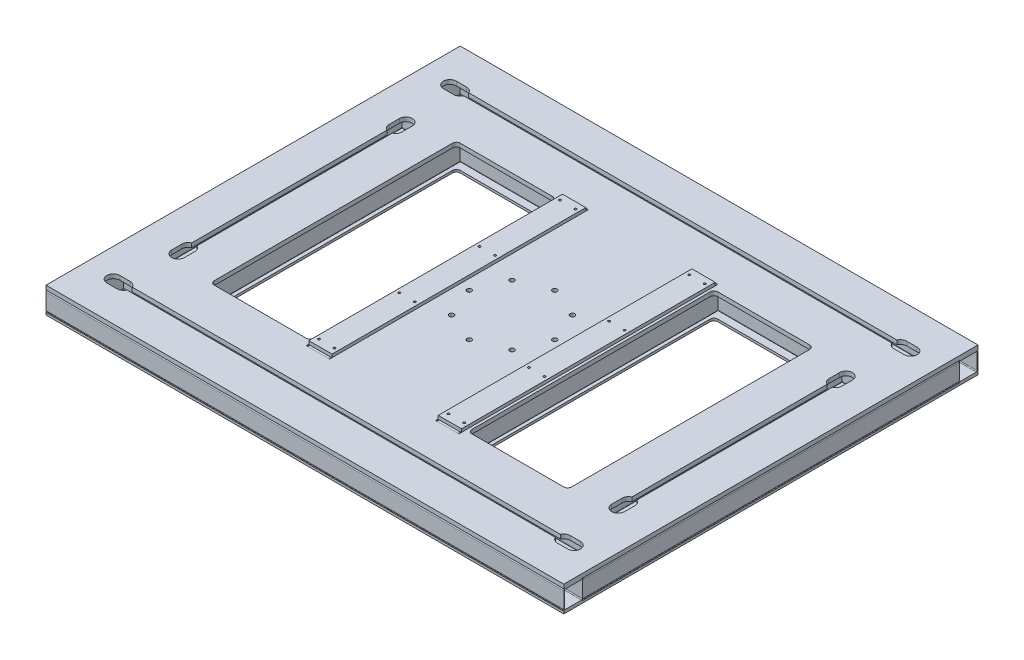
SolidWorks part; units mm, degrees
ref_plane "正面" through (0, 0, 0) normal (0, 0, 1) x (1, 0, 0)
ref_plane "平面" through (0, 0, 0) normal (0, 1, 0) x (1, 0, 0)
ref_plane "右側面" through (0, 0, 0) normal (1, 0, 0) x (0, 0, -1)
sketch "ｽｹｯﾁ1" plane through (0, 0, 0) normal (0, 1, 0) x (1, 0, 0)
  line L0 (-1000, -800) -> (1000, -800)
  line L1 (1000, -800) -> (1000, 800)
  line L2 (1000, 800) -> (-1000, 800)
  line L3 (-1000, 800) -> (-1000, -800)
extrude "ﾎﾞｽ - 押し出し1" add sketch "ｽｹｯﾁ1" along normal blind 9
sketch "ｽｹｯﾁ2" plane through (0, 0, 0) normal (0, 1, 0) x (1, 0, 0)
  line L0 (-675, -475) -> (-320, -475)
  line L1 (-305, -460) -> (-305, 460)
  line L2 (-320, 475) -> (-675, 475)
  line L3 (-690, 460) -> (-690, -460)
  line L4 (320, -475) -> (675, -475)
  line L5 (690, -460) -> (690, 460)
  line L6 (675, 475) -> (320, 475)
  line L7 (305, 460) -> (305, -460)
  arc A0 (-320, -475) -> (-305, -460) centre (-320, -460) ccw
  arc A1 (-305, 460) -> (-320, 475) centre (-320, 460) ccw
  arc A2 (-675, 475) -> (-690, 460) centre (-675, 460) ccw
  arc A3 (-690, -460) -> (-675, -475) centre (-675, -460) ccw
  arc A4 (675, -475) -> (690, -460) centre (675, -460) ccw
  arc A5 (690, 460) -> (675, 475) centre (675, 460) ccw
  arc A6 (320, 475) -> (305, 460) centre (320, 460) ccw
  arc A7 (305, -460) -> (320, -475) centre (320, -460) ccw
extrude "ｶｯﾄ - 押し出し1" cut sketch "ｽｹｯﾁ2" against normal through all and the other way through all
sketch "ｽｹｯﾁ3" plane through (0, 0, 0) normal (0, 1, 0) x (1, 0, 0)
  line L0 (-885, -475) -> (-815, -475)
  line L1 (-800, -460) -> (-800, 460)
  line L2 (-815, 475) -> (-885, 475)
  line L3 (-900, 460) -> (-900, -460)
  line L4 (815, -475) -> (885, -475)
  line L5 (900, -460) -> (900, 460)
  line L6 (885, 475) -> (815, 475)
  line L7 (800, 460) -> (800, -460)
  arc A0 (-815, -475) -> (-800, -460) centre (-815, -460) ccw
  arc A1 (-800, 460) -> (-815, 475) centre (-815, 460) ccw
  arc A2 (-885, 475) -> (-900, 460) centre (-885, 460) ccw
  arc A3 (-900, -460) -> (-885, -475) centre (-885, -460) ccw
  arc A4 (885, -475) -> (900, -460) centre (885, -460) ccw
  arc A5 (900, 460) -> (885, 475) centre (885, 460) ccw
  arc A6 (815, 475) -> (800, 460) centre (815, 460) ccw
  arc A7 (800, -460) -> (815, -475) centre (815, -460) ccw
extrude "ｶｯﾄ - 押し出し2" cut sketch "ｽｹｯﾁ3" against normal through all and the other way through all
sketch "ｽｹｯﾁ4" plane through (0, 0, 0) normal (0, 1, 0) x (1, 0, 0)
  line L0 (-885, -700) -> (885, -700)
  line L1 (900, -685) -> (900, -615)
  line L2 (885, -600) -> (-885, -600)
  line L3 (-900, -615) -> (-900, -685)
  line L4 (-885, 600) -> (885, 600)
  line L5 (900, 615) -> (900, 685)
  line L6 (885, 700) -> (-885, 700)
  line L7 (-900, 685) -> (-900, 615)
  arc A0 (885, -700) -> (900, -685) centre (885, -685) ccw
  arc A1 (900, -615) -> (885, -600) centre (885, -615) ccw
  arc A2 (-885, -600) -> (-900, -615) centre (-885, -615) ccw
  arc A3 (-900, -685) -> (-885, -700) centre (-885, -685) ccw
  arc A4 (885, 600) -> (900, 615) centre (885, 615) ccw
  arc A5 (900, 685) -> (885, 700) centre (885, 685) ccw
  arc A6 (-885, 700) -> (-900, 685) centre (-885, 685) ccw
  arc A7 (-900, 615) -> (-885, 600) centre (-885, 615) ccw
extrude "ｶｯﾄ - 押し出し3" cut sketch "ｽｹｯﾁ4" against normal through all and the other way through all
sketch "ｽｹｯﾁ5" plane through (0, 0, 0) normal (1, 0, 0) x (0, 0, -1)
  line L0 (-793.6, 9) -> (-731.4, 9)
  line L1 (-725, 15.4) -> (-725, 77.6)
  line L2 (-731.4, 84) -> (-793.6, 84)
  line L3 (-800, 77.6) -> (-800, 15.4)
  line L4 (-793.6, 12.2) -> (-731.4, 12.2)
  line L5 (-728.2, 15.4) -> (-728.2, 77.6)
  line L6 (-731.4, 80.8) -> (-793.6, 80.8)
  line L7 (-796.8, 77.6) -> (-796.8, 15.4)
  line L8 (731.4, 9) -> (793.6, 9)
  line L9 (800, 15.4) -> (800, 77.6)
  line L10 (793.6, 84) -> (731.4, 84)
  line L11 (725, 77.6) -> (725, 15.4)
  line L12 (731.4, 12.2) -> (793.6, 12.2)
  line L13 (796.8, 15.4) -> (796.8, 77.6)
  line L14 (793.6, 80.8) -> (731.4, 80.8)
  line L15 (728.2, 77.6) -> (728.2, 15.4)
  arc A0 (-731.4, 9) -> (-725, 15.4) centre (-731.4, 15.4) ccw
  arc A1 (-725, 77.6) -> (-731.4, 84) centre (-731.4, 77.6) ccw
  arc A2 (-793.6, 84) -> (-800, 77.6) centre (-793.6, 77.6) ccw
  arc A3 (-800, 15.4) -> (-793.6, 9) centre (-793.6, 15.4) ccw
  arc A4 (-731.4, 12.2) -> (-728.2, 15.4) centre (-731.4, 15.4) ccw
  arc A5 (-728.2, 77.6) -> (-731.4, 80.8) centre (-731.4, 77.6) ccw
  arc A6 (-793.6, 80.8) -> (-796.8, 77.6) centre (-793.6, 77.6) ccw
  arc A7 (-796.8, 15.4) -> (-793.6, 12.2) centre (-793.6, 15.4) ccw
  arc A8 (793.6, 9) -> (800, 15.4) centre (793.6, 15.4) ccw
  arc A9 (800, 77.6) -> (793.6, 84) centre (793.6, 77.6) ccw
  arc A10 (731.4, 84) -> (725, 77.6) centre (731.4, 77.6) ccw
  arc A11 (725, 15.4) -> (731.4, 9) centre (731.4, 15.4) ccw
  arc A12 (793.6, 12.2) -> (796.8, 15.4) centre (793.6, 15.4) ccw
  arc A13 (796.8, 77.6) -> (793.6, 80.8) centre (793.6, 77.6) ccw
  arc A14 (731.4, 80.8) -> (728.2, 77.6) centre (731.4, 77.6) ccw
  arc A15 (728.2, 15.4) -> (731.4, 12.2) centre (731.4, 15.4) ccw
extrude "ﾎﾞｽ - 押し出し2" add sketch "ｽｹｯﾁ5" against normal blind 1000 and the other way blind 1000
sketch "ｽｹｯﾁ6" plane through (0, 0, 0) normal (1, 0, 0) x (0, 0, -1)
  line L0 (-568.6, 9) -> (-506.4, 9)
  line L1 (-500, 15.4) -> (-500, 77.6)
  line L2 (-506.4, 84) -> (-568.6, 84)
  line L3 (-575, 77.6) -> (-575, 15.4)
  line L4 (-568.6, 12.2) -> (-506.4, 12.2)
  line L5 (-503.2, 15.4) -> (-503.2, 77.6)
  line L6 (-506.4, 80.8) -> (-568.6, 80.8)
  line L7 (-571.8, 77.6) -> (-571.8, 15.4)
  line L8 (506.4, 9) -> (568.6, 9)
  line L9 (575, 15.4) -> (575, 77.6)
  line L10 (568.6, 84) -> (506.4, 84)
  line L11 (500, 77.6) -> (500, 15.4)
  line L12 (506.4, 12.2) -> (568.6, 12.2)
  line L13 (571.8, 15.4) -> (571.8, 77.6)
  line L14 (568.6, 80.8) -> (506.4, 80.8)
  line L15 (503.2, 77.6) -> (503.2, 15.4)
  arc A0 (-506.4, 9) -> (-500, 15.4) centre (-506.4, 15.4) ccw
  arc A1 (-500, 77.6) -> (-506.4, 84) centre (-506.4, 77.6) ccw
  arc A2 (-568.6, 84) -> (-575, 77.6) centre (-568.6, 77.6) ccw
  arc A3 (-575, 15.4) -> (-568.6, 9) centre (-568.6, 15.4) ccw
  arc A4 (-506.4, 12.2) -> (-503.2, 15.4) centre (-506.4, 15.4) ccw
  arc A5 (-503.2, 77.6) -> (-506.4, 80.8) centre (-506.4, 77.6) ccw
  arc A6 (-568.6, 80.8) -> (-571.8, 77.6) centre (-568.6, 77.6) ccw
  arc A7 (-571.8, 15.4) -> (-568.6, 12.2) centre (-568.6, 15.4) ccw
  arc A8 (568.6, 9) -> (575, 15.4) centre (568.6, 15.4) ccw
  arc A9 (575, 77.6) -> (568.6, 84) centre (568.6, 77.6) ccw
  arc A10 (506.4, 84) -> (500, 77.6) centre (506.4, 77.6) ccw
  arc A11 (500, 15.4) -> (506.4, 9) centre (506.4, 15.4) ccw
  arc A12 (568.6, 12.2) -> (571.8, 15.4) centre (568.6, 15.4) ccw
  arc A13 (571.8, 77.6) -> (568.6, 80.8) centre (568.6, 77.6) ccw
  arc A14 (506.4, 80.8) -> (503.2, 77.6) centre (506.4, 77.6) ccw
  arc A15 (503.2, 15.4) -> (506.4, 12.2) centre (506.4, 15.4) ccw
extrude "ﾎﾞｽ - 押し出し3" add sketch "ｽｹｯﾁ6" against normal blind 925 and the other way blind 925
sketch "ｽｹｯﾁ7" plane through (0, 0, 0) normal (0, 0, 1) x (1, 0, 0)
  line L0 (-993.6, 9) -> (-931.4, 9)
  line L1 (-925, 15.4) -> (-925, 77.6)
  line L2 (-931.4, 84) -> (-993.6, 84)
  line L3 (-1000, 77.6) -> (-1000, 15.4)
  line L4 (-993.6, 12.2) -> (-931.4, 12.2)
  line L5 (-928.2, 15.4) -> (-928.2, 77.6)
  line L6 (-931.4, 80.8) -> (-993.6, 80.8)
  line L7 (-996.8, 77.6) -> (-996.8, 15.4)
  line L8 (931.4, 9) -> (993.6, 9)
  line L9 (1000, 15.4) -> (1000, 77.6)
  line L10 (993.6, 84) -> (931.4, 84)
  line L11 (925, 77.6) -> (925, 15.4)
  line L12 (931.4, 12.2) -> (993.6, 12.2)
  line L13 (996.8, 15.4) -> (996.8, 77.6)
  line L14 (993.6, 80.8) -> (931.4, 80.8)
  line L15 (928.2, 77.6) -> (928.2, 15.4)
  arc A0 (-931.4, 9) -> (-925, 15.4) centre (-931.4, 15.4) ccw
  arc A1 (-925, 77.6) -> (-931.4, 84) centre (-931.4, 77.6) ccw
  arc A2 (-993.6, 84) -> (-1000, 77.6) centre (-993.6, 77.6) ccw
  arc A3 (-1000, 15.4) -> (-993.6, 9) centre (-993.6, 15.4) ccw
  arc A4 (-931.4, 12.2) -> (-928.2, 15.4) centre (-931.4, 15.4) ccw
  arc A5 (-928.2, 77.6) -> (-931.4, 80.8) centre (-931.4, 77.6) ccw
  arc A6 (-993.6, 80.8) -> (-996.8, 77.6) centre (-993.6, 77.6) ccw
  arc A7 (-996.8, 15.4) -> (-993.6, 12.2) centre (-993.6, 15.4) ccw
  arc A8 (993.6, 9) -> (1000, 15.4) centre (993.6, 15.4) ccw
  arc A9 (1000, 77.6) -> (993.6, 84) centre (993.6, 77.6) ccw
  arc A10 (931.4, 84) -> (925, 77.6) centre (931.4, 77.6) ccw
  arc A11 (925, 15.4) -> (931.4, 9) centre (931.4, 15.4) ccw
  arc A12 (993.6, 12.2) -> (996.8, 15.4) centre (993.6, 15.4) ccw
  arc A13 (996.8, 77.6) -> (993.6, 80.8) centre (993.6, 77.6) ccw
  arc A14 (931.4, 80.8) -> (928.2, 77.6) centre (931.4, 77.6) ccw
  arc A15 (928.2, 15.4) -> (931.4, 12.2) centre (931.4, 15.4) ccw
extrude "ﾎﾞｽ - 押し出し4" add sketch "ｽｹｯﾁ7" against normal blind 725 and the other way blind 725
sketch "ｽｹｯﾁ8" plane through (0, 0, 0) normal (0, 0, 1) x (1, 0, 0)
  line L0 (-768.6, 9) -> (-706.4, 9)
  line L1 (-700, 15.4) -> (-700, 77.6)
  line L2 (-706.4, 84) -> (-768.6, 84)
  line L3 (-775, 77.6) -> (-775, 15.4)
  line L4 (-768.6, 12.2) -> (-706.4, 12.2)
  line L5 (-703.2, 15.4) -> (-703.2, 77.6)
  line L6 (-706.4, 80.8) -> (-768.6, 80.8)
  line L7 (-771.8, 77.6) -> (-771.8, 15.4)
  line L8 (706.4, 9) -> (768.6, 9)
  line L9 (775, 15.4) -> (775, 77.6)
  line L10 (768.6, 84) -> (706.4, 84)
  line L11 (700, 77.6) -> (700, 15.4)
  line L12 (706.4, 12.2) -> (768.6, 12.2)
  line L13 (771.8, 15.4) -> (771.8, 77.6)
  line L14 (768.6, 80.8) -> (706.4, 80.8)
  line L15 (703.2, 77.6) -> (703.2, 15.4)
  arc A0 (-706.4, 9) -> (-700, 15.4) centre (-706.4, 15.4) ccw
  arc A1 (-700, 77.6) -> (-706.4, 84) centre (-706.4, 77.6) ccw
  arc A2 (-768.6, 84) -> (-775, 77.6) centre (-768.6, 77.6) ccw
  arc A3 (-775, 15.4) -> (-768.6, 9) centre (-768.6, 15.4) ccw
  arc A4 (-706.4, 12.2) -> (-703.2, 15.4) centre (-706.4, 15.4) ccw
  arc A5 (-703.2, 77.6) -> (-706.4, 80.8) centre (-706.4, 77.6) ccw
  arc A6 (-768.6, 80.8) -> (-771.8, 77.6) centre (-768.6, 77.6) ccw
  arc A7 (-771.8, 15.4) -> (-768.6, 12.2) centre (-768.6, 15.4) ccw
  arc A8 (768.6, 9) -> (775, 15.4) centre (768.6, 15.4) ccw
  arc A9 (775, 77.6) -> (768.6, 84) centre (768.6, 77.6) ccw
  arc A10 (706.4, 84) -> (700, 77.6) centre (706.4, 77.6) ccw
  arc A11 (700, 15.4) -> (706.4, 9) centre (706.4, 15.4) ccw
  arc A12 (768.6, 12.2) -> (771.8, 15.4) centre (768.6, 15.4) ccw
  arc A13 (771.8, 77.6) -> (768.6, 80.8) centre (768.6, 77.6) ccw
  arc A14 (706.4, 80.8) -> (703.2, 77.6) centre (706.4, 77.6) ccw
  arc A15 (703.2, 15.4) -> (706.4, 12.2) centre (706.4, 15.4) ccw
extrude "ﾎﾞｽ - 押し出し5" add sketch "ｽｹｯﾁ8" against normal blind 500 and the other way blind 500
ref_plane "平面1" through (0, 84, 0) normal (0, 1, 0) x (1, 0, 0)
sketch "ｽｹｯﾁ10" plane through (0, 84, 0) normal (0, 1, 0) x (1, 0, 0)
  line L0 (-1000, -800) -> (1000, -800)
  line L1 (1000, -800) -> (1000, 800)
  line L2 (1000, 800) -> (-1000, 800)
  line L3 (-1000, 800) -> (-1000, -800)
extrude "ﾎﾞｽ - 押し出し6" add sketch "ｽｹｯﾁ10" along normal blind 16
sketch "ｽｹｯﾁ11" plane through (0, 0, 0) normal (0, 1, 0) x (1, 0, 0)
  line L0 (-675, -475) -> (-320, -475)
  line L1 (-305, -460) -> (-305, 460)
  line L2 (-320, 475) -> (-675, 475)
  line L3 (-690, 460) -> (-690, -460)
  line L4 (320, -475) -> (675, -475)
  line L5 (690, -460) -> (690, 460)
  line L6 (675, 475) -> (320, 475)
  line L7 (305, 460) -> (305, -460)
  arc A0 (-320, -475) -> (-305, -460) centre (-320, -460) ccw
  arc A1 (-305, 460) -> (-320, 475) centre (-320, 460) ccw
  arc A2 (-675, 475) -> (-690, 460) centre (-675, 460) ccw
  arc A3 (-690, -460) -> (-675, -475) centre (-675, -460) ccw
  arc A4 (675, -475) -> (690, -460) centre (675, -460) ccw
  arc A5 (690, 460) -> (675, 475) centre (675, 460) ccw
  arc A6 (320, 475) -> (305, 460) centre (320, 460) ccw
  arc A7 (305, -460) -> (320, -475) centre (320, -460) ccw
extrude "ｶｯﾄ - 押し出し4" cut sketch "ｽｹｯﾁ11" against normal through all and the other way through all
ref_plane "平面2" through (0, 100, 0) normal (0, 1, 0) x (1, 0, 0)
sketch "ｽｹｯﾁ13" plane through (0, 100, 0) normal (0, 1, 0) x (1, 0, 0)
  line L0 (-205, -500) -> (-295, -500)
  line L1 (-295, -500) -> (-295, 500)
  line L2 (-295, 500) -> (-205, 500)
  line L3 (-205, 500) -> (-205, -500)
  line L4 (205, -500) -> (295, -500)
  line L5 (295, -500) -> (295, 500)
  line L6 (295, 500) -> (205, 500)
  line L7 (205, 500) -> (205, -500)
extrude "ｶｯﾄ - 押し出し5" cut sketch "ｽｹｯﾁ13" against normal blind 16
sketch "ｽｹｯﾁ14" plane through (0, 0, 0) normal (0, 0, 1) x (1, 0, 0)
  line L0 (-290.4, 9) -> (-209.6, 9)
  line L1 (-205, 13.6) -> (-205, 94.4)
  line L2 (-209.6, 99) -> (-290.4, 99)
  line L3 (-295, 94.4) -> (-295, 13.6)
  line L4 (-290.4, 11.3) -> (-209.6, 11.3)
  line L5 (-207.3, 13.6) -> (-207.3, 94.4)
  line L6 (-209.6, 96.7) -> (-290.4, 96.7)
  line L7 (-292.7, 94.4) -> (-292.7, 13.6)
  line L8 (209.6, 9) -> (290.4, 9)
  line L9 (295, 13.6) -> (295, 94.4)
  line L10 (290.4, 99) -> (209.6, 99)
  line L11 (205, 94.4) -> (205, 13.6)
  line L12 (209.6, 11.3) -> (290.4, 11.3)
  line L13 (292.7, 13.6) -> (292.7, 94.4)
  line L14 (290.4, 96.7) -> (209.6, 96.7)
  line L15 (207.3, 94.4) -> (207.3, 13.6)
  arc A0 (-209.6, 9) -> (-205, 13.6) centre (-209.6, 13.6) ccw
  arc A1 (-205, 94.4) -> (-209.6, 99) centre (-209.6, 94.4) ccw
  arc A2 (-290.4, 99) -> (-295, 94.4) centre (-290.4, 94.4) ccw
  arc A3 (-295, 13.6) -> (-290.4, 9) centre (-290.4, 13.6) ccw
  arc A4 (-209.6, 11.3) -> (-207.3, 13.6) centre (-209.6, 13.6) ccw
  arc A5 (-207.3, 94.4) -> (-209.6, 96.7) centre (-209.6, 94.4) ccw
  arc A6 (-290.4, 96.7) -> (-292.7, 94.4) centre (-290.4, 94.4) ccw
  arc A7 (-292.7, 13.6) -> (-290.4, 11.3) centre (-290.4, 13.6) ccw
  arc A8 (290.4, 9) -> (295, 13.6) centre (290.4, 13.6) ccw
  arc A9 (295, 94.4) -> (290.4, 99) centre (290.4, 94.4) ccw
  arc A10 (209.6, 99) -> (205, 94.4) centre (209.6, 94.4) ccw
  arc A11 (205, 13.6) -> (209.6, 9) centre (209.6, 13.6) ccw
  arc A12 (290.4, 11.3) -> (292.7, 13.6) centre (290.4, 13.6) ccw
  arc A13 (292.7, 94.4) -> (290.4, 96.7) centre (290.4, 94.4) ccw
  arc A14 (209.6, 96.7) -> (207.3, 94.4) centre (209.6, 94.4) ccw
  arc A15 (207.3, 13.6) -> (209.6, 11.3) centre (209.6, 13.6) ccw
extrude "ﾎﾞｽ - 押し出し7" add sketch "ｽｹｯﾁ14" against normal blind 500 and the other way blind 500
ref_plane "平面3" through (0, 99, 0) normal (0, 1, 0) x (1, 0, 0)
sketch "ｽｹｯﾁ16" plane through (0, 99, 0) normal (0, 1, 0) x (1, 0, 0)
  line L0 (-205, -490) -> (-295, -490)
  line L1 (-295, -490) -> (-295, 490)
  line L2 (-295, 490) -> (-205, 490)
  line L3 (-205, 490) -> (-205, -490)
extrude "ﾎﾞｽ - 押し出し8" add sketch "ｽｹｯﾁ16" along normal blind 13
sketch "ｽｹｯﾁ17" plane through (0, 99, 0) normal (0, 1, 0) x (1, 0, 0)
  line L0 (205, -490) -> (295, -490)
  line L1 (295, -490) -> (295, 490)
  line L2 (295, 490) -> (205, 490)
  line L3 (205, 490) -> (205, -490)
extrude "ﾎﾞｽ - 押し出し9" add sketch "ｽｹｯﾁ17" along normal blind 13
sketch "ｽｹｯﾁ18" plane through (0, 100, 0) normal (0, 1, 0) x (1, 0, 0)
  line L0 (-890, -675) -> (-850, -675)
  line L1 (-827.0871, -660) -> (827.0871, -660)
  line L2 (850, -675) -> (890, -675)
  line L3 (890, -625) -> (850, -625)
  line L4 (827.0871, -640) -> (-827.0871, -640)
  line L5 (-850, -625) -> (-890, -625)
  line L6 (-890, 625) -> (-850, 625)
  line L7 (-827.0871, 640) -> (827.0871, 640)
  line L8 (850, 625) -> (890, 625)
  line L9 (890, 675) -> (850, 675)
  line L10 (827.0871, 660) -> (-827.0871, 660)
  line L11 (-850, 675) -> (-890, 675)
  arc A0 (-850, -675) -> (-827.0871, -660) centre (-850, -650) ccw
  arc A1 (827.0871, -660) -> (850, -675) centre (850, -650) ccw
  arc A2 (890, -675) -> (915, -650) centre (890, -650) ccw
  arc A3 (915, -650) -> (890, -625) centre (890, -650) ccw
  arc A4 (850, -625) -> (827.0871, -640) centre (850, -650) ccw
  arc A5 (-827.0871, -640) -> (-850, -625) centre (-850, -650) ccw
  arc A6 (-890, -625) -> (-915, -650) centre (-890, -650) ccw
  arc A7 (-915, -650) -> (-890, -675) centre (-890, -650) ccw
  arc A8 (-850, 625) -> (-827.0871, 640) centre (-850, 650) ccw
  arc A9 (827.0871, 640) -> (850, 625) centre (850, 650) ccw
  arc A10 (890, 625) -> (915, 650) centre (890, 650) ccw
  arc A11 (915, 650) -> (890, 675) centre (890, 650) ccw
  arc A12 (850, 675) -> (827.0871, 660) centre (850, 650) ccw
  arc A13 (-827.0871, 660) -> (-850, 675) centre (-850, 650) ccw
  arc A14 (-890, 675) -> (-915, 650) centre (-890, 650) ccw
  arc A15 (-915, 650) -> (-890, 625) centre (-890, 650) ccw
extrude "ｶｯﾄ - 押し出し6" cut sketch "ｽｹｯﾁ18" against normal blind 16
sketch "ｽｹｯﾁ19" plane through (0, 100, 0) normal (0, 1, 0) x (1, 0, 0)
  line L0 (-875, -440) -> (-875, -400)
  line L1 (-860, -377.0871) -> (-860, 377.0871)
  line L2 (-875, 400) -> (-875, 440)
  line L3 (-825, 440) -> (-825, 400)
  line L4 (-840, 377.0871) -> (-840, -377.0871)
  line L5 (-825, -400) -> (-825, -440)
  line L6 (825, -440) -> (825, -400)
  line L7 (840, -377.0871) -> (840, 377.0871)
  line L8 (825, 400) -> (825, 440)
  line L9 (875, 440) -> (875, 400)
  line L10 (860, 377.0871) -> (860, -377.0871)
  line L11 (875, -400) -> (875, -440)
  arc A0 (-875, -400) -> (-860, -377.0871) centre (-850, -400) cw
  arc A1 (-860, 377.0871) -> (-875, 400) centre (-850, 400) cw
  arc A2 (-875, 440) -> (-850, 465) centre (-850, 440) cw
  arc A3 (-850, 465) -> (-825, 440) centre (-850, 440) cw
  arc A4 (-825, 400) -> (-840, 377.0871) centre (-850, 400) cw
  arc A5 (-840, -377.0871) -> (-825, -400) centre (-850, -400) cw
  arc A6 (-825, -440) -> (-850, -465) centre (-850, -440) cw
  arc A7 (-850, -465) -> (-875, -440) centre (-850, -440) cw
  arc A8 (825, -400) -> (840, -377.0871) centre (850, -400) cw
  arc A9 (840, 377.0871) -> (825, 400) centre (850, 400) cw
  arc A10 (825, 440) -> (850, 465) centre (850, 440) cw
  arc A11 (850, 465) -> (875, 440) centre (850, 440) cw
  arc A12 (875, 400) -> (860, 377.0871) centre (850, 400) cw
  arc A13 (860, -377.0871) -> (875, -400) centre (850, -400) cw
  arc A14 (875, -440) -> (850, -465) centre (850, -440) cw
  arc A15 (850, -465) -> (825, -440) centre (850, -440) cw
extrude "ｶｯﾄ - 押し出し7" cut sketch "ｽｹｯﾁ19" against normal blind 16
sketch "ｽｹｯﾁ20" plane through (0, 0, 0) normal (0, 1, 0) x (1, 0, 0)
  circle A0 centre (165, 0) radius 9
  circle A1 centre (116.6726, 116.6726) radius 9
  circle A2 centre (0, 165) radius 9
  circle A3 centre (-116.6726, 116.6726) radius 9
  circle A4 centre (-165, 0) radius 9
  circle A5 centre (-116.6726, -116.6726) radius 9
  circle A6 centre (0, -165) radius 9
  circle A7 centre (116.6726, -116.6726) radius 9
extrude "ｶｯﾄ - 押し出し8" cut sketch "ｽｹｯﾁ20" against normal through all and the other way through all
ref_plane "平面4" through (0, 112, 0) normal (0, 1, 0) x (1, 0, 0)
sketch "ｽｹｯﾁ22" plane through (0, 112, 0) normal (0, 1, 0) x (1, 0, 0)
  circle A0 centre (-220, -155) radius 4.188
  circle A1 centre (-220, -465) radius 4.188
  circle A2 centre (-220, 155) radius 4.188
  circle A3 centre (-220, 465) radius 4.188
  circle A4 centre (-280, -155) radius 4.188
  circle A5 centre (-280, -465) radius 4.188
  circle A6 centre (-280, 155) radius 4.188
  circle A7 centre (-280, 465) radius 4.188
  circle A8 centre (220, -155) radius 4.188
  circle A9 centre (220, -465) radius 4.188
  circle A10 centre (220, 155) radius 4.188
  circle A11 centre (220, 465) radius 4.188
  circle A12 centre (280, -155) radius 4.188
  circle A13 centre (280, -465) radius 4.188
  circle A14 centre (280, 155) radius 4.188
  circle A15 centre (280, 465) radius 4.188
extrude "ｶｯﾄ - 押し出し9" cut sketch "ｽｹｯﾁ22" against normal blind 15.3
